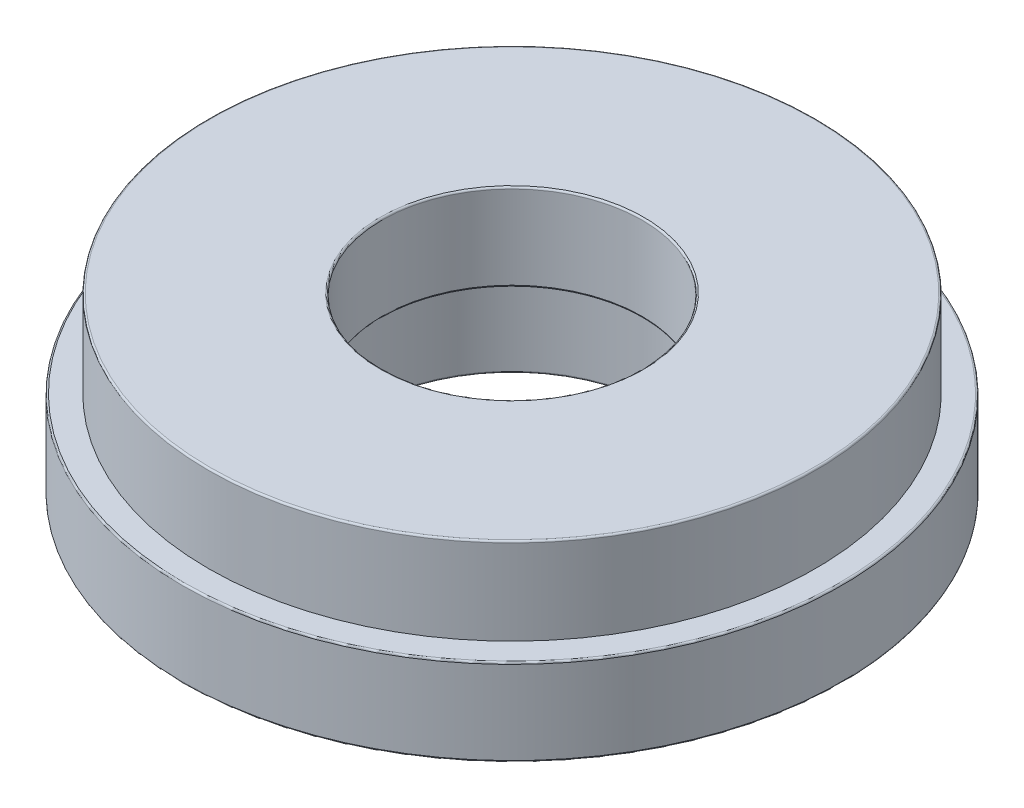
SolidWorks part; units mm, degrees
ref_plane "前视基准面" through (0, 0, 0) normal (0, 0, 1) x (1, 0, 0)
ref_plane "上视基准面" through (0, 0, 0) normal (0, 1, 0) x (1, 0, 0)
ref_plane "右视基准面" through (0, 0, 0) normal (1, 0, 0) x (0, 0, -1)
other "Configuration Table"
sketch "草图1" plane through (0, 0, 0) normal (0, 1, 0) x (1, 0, 0)
  circle A0 centre (0, 0) radius 19
  circle A1 centre (0, 0) radius 15 construction
  circle A2 centre (0, 15) radius 3.05
  circle A3 centre (12.9904, 7.5) radius 3.05
  circle A4 centre (12.9904, -7.5) radius 3.05
  circle A5 centre (0, -15) radius 3.05
  circle A6 centre (-12.9904, -7.5) radius 3.05
  circle A7 centre (-12.9904, 7.5) radius 3.05
  point P18 (0, 0)
  dimension "D1" = 6.1
  dimension "D2" = 38
  dimension "D3" = 30
  dimension "D4" = 6
extrude "凸台-拉伸1" add sketch "草图1" along normal blind 5 contours A0
extrude "切除-拉伸1" cut sketch "草图1<3>" along normal blind 4 contours A7 | A6 | A5 | A4 | A3 | A2 region at (0, 0, -15) region at (12.9904, 0, -7.5) region at (12.9904, 0, 7.5) region at (0, 0, 15) region at (-12.9904, 0, 7.5) region at (-12.9904, 0, -7.5)
sketch "草图1<3>" plane through (0, 0, 0) normal (0, 1, 0) x (1, 0, 0) same geometry as "草图1"
sketch "草图5" plane through (0, 5, 0) normal (0, 1, 0) x (1, 0, 0)
  circle A0 centre (0, 0) radius 7.5
  circle A1 centre (0, 0) radius 17.5
  dimension "D1" = 35
  dimension "D2" = 15
extrude "凸台-拉伸3" add sketch "草图5" along normal blind 5
sketch "草图8" plane through (0, 0, 0) normal (0, -1, 0) x (1, 0, 0)
  circle A0 centre (0, 0) radius 8.5
  dimension "D1" = 17
extrude "切除-拉伸4" cut sketch "草图8" against normal offset from surface (5 mm away) 5 up to face at (0, 10, 17.5)
fillet "圆角1" radius 0.1 12 edges at (0, 5, 7.5) (-12.9904, 0, -4.45) (-12.9904, 0, 10.55) (0, 0, 18.05) (12.9904, 0, 10.55) (12.9904, 0, -4.45) (0, 0, -11.95) (0, 0, -8.5) (0, 10, 7.5) (0, 10, 17.5) (0, 0, 19) (0, 5, 19)
